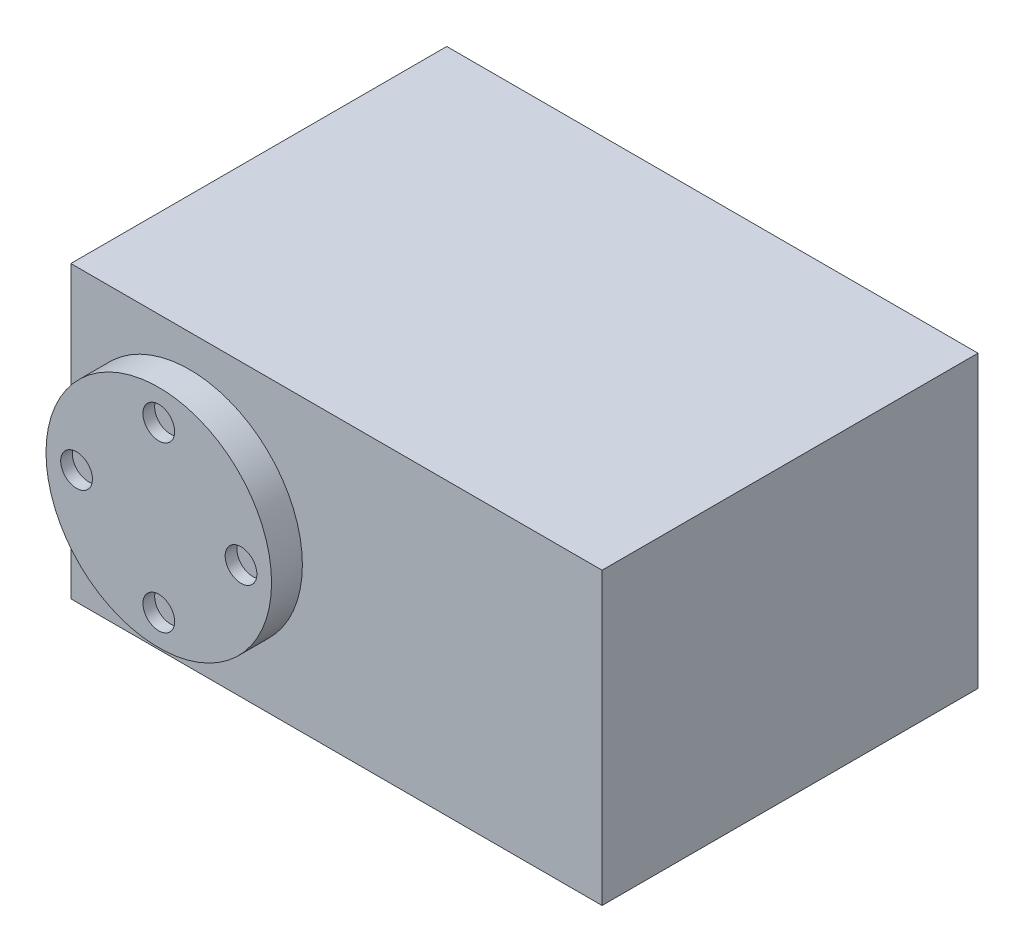
SolidWorks part; units mm, degrees
ref_plane "Front Plane" through (0, 0, 0) normal (0, 0, 1) x (1, 0, 0)
ref_plane "Top Plane" through (0, 0, 0) normal (0, 1, 0) x (1, 0, 0)
ref_plane "Right Plane" through (0, 0, 0) normal (1, 0, 0) x (0, 0, -1)
ref_plane "PZ_m16_000" through (0, 0, -16) normal (0, 0, 1) x (1, 0, 0)
sketch "S_box1" plane through (0, 0, -16) normal (0, 0, 1) x (1, 0, 0)
  line L0 (-10.11, -12.36) -> (35.11, -12.36)
  line L1 (35.11, -12.36) -> (35.11, 12.36)
  line L2 (35.11, 12.36) -> (-10.11, 12.36)
  line L3 (-10.11, 12.36) -> (-10.11, -12.36)
  dimension "P1" = 10.11
  dimension "P2" = 12.36
  dimension "P3" = 35.11
  dimension "P4" = 12.36
  dimension "P5" = 35.11
  dimension "P6" = 12.36
  dimension "P7" = 10.11
  dimension "P8" = 12.36
extrude "Boss_1" add sketch "S_box1" along normal blind 32
ref_plane "PZ_p15_500" through (0, 0, 15.5) normal (0, 0, 1) x (1, 0, 0)
sketch "S_cyl2" plane through (0, 0, 15.5) normal (0, 0, 1) x (1, 0, 0)
  circle A0 centre (0, 0) radius 9.6
  dimension "D1_S_cyl2" = 19.2
extrude "Boss_2" add sketch "S_cyl2" along normal blind 3.125
ref_plane "PZ_m18_625" through (0, 0, -18.625) normal (0, 0, 1) x (1, 0, 0)
sketch "S_cyl3" plane through (0, 0, -18.625) normal (0, 0, 1) x (1, 0, 0)
  circle A0 centre (0, 0) radius 9.6
  dimension "D1_S_cyl3" = 19.2
extrude "Boss_3" add sketch "S_cyl3" along normal blind 3.125
ref_plane "PZ_p17_625" through (0, 0, 17.625) normal (0, 0, 1) x (1, 0, 0)
sketch "S_hole4" plane through (0, 0, 17.625) normal (0, 0, 1) x (1, 0, 0)
  circle A0 centre (7, 0) radius 1.35
  dimension "D1_S_hole4" = 2.7
  dimension "P2" = 7
extrude "Hole_4" cut sketch "S_hole4" along normal blind 1.1
sketch "S_hole5" plane through (0, 0, 17.625) normal (0, 0, 1) x (1, 0, 0)
  circle A0 centre (0, 7) radius 1.35
  dimension "D1_S_hole5" = 2.7
  dimension "P2" = 7
extrude "Hole_5" cut sketch "S_hole5" along normal blind 1.1
sketch "S_hole6" plane through (0, 0, 17.625) normal (0, 0, 1) x (1, 0, 0)
  circle A0 centre (-7, 0) radius 1.35
  dimension "D1_S_hole6" = 2.7
  dimension "P2" = 7
extrude "Hole_6" cut sketch "S_hole6" along normal blind 1.1
sketch "S_hole7" plane through (0, 0, 17.625) normal (0, 0, 1) x (1, 0, 0)
  circle A0 centre (0, -7) radius 1.35
  dimension "D1_S_hole7" = 2.7
  dimension "P2" = 7
extrude "Hole_7" cut sketch "S_hole7" along normal blind 1.1
equation "\"plate_t\" = 3"
equation "\"clearance\" = 0.4"
